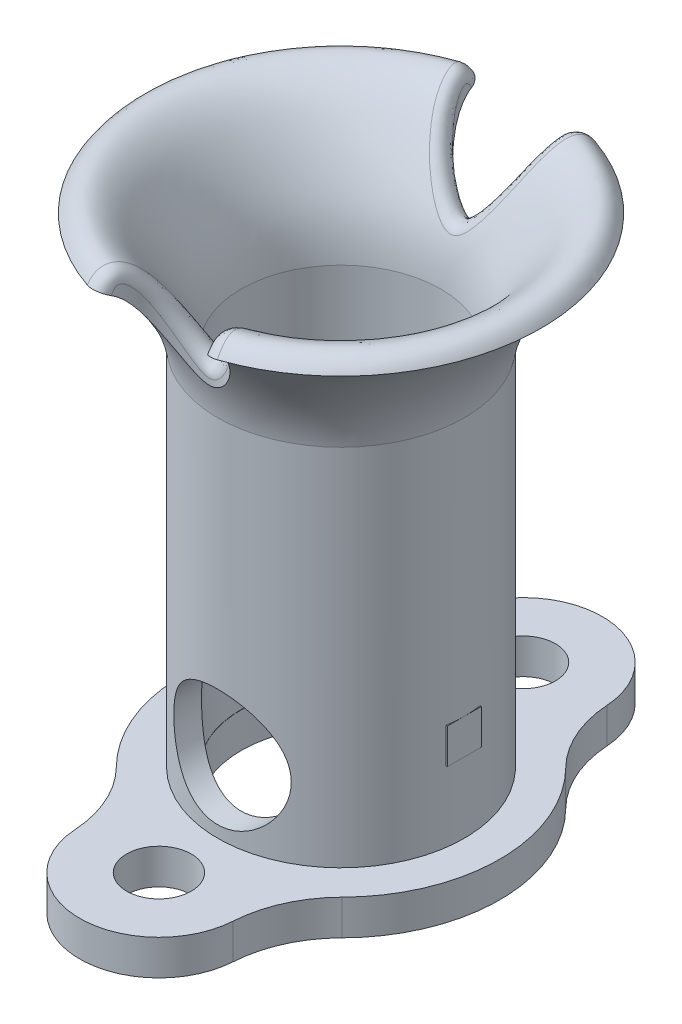
SolidWorks part; units mm, degrees
ref_plane "Front Plane" through (0, 0, 0) normal (0, 0, 1) x (1, 0, 0)
ref_plane "Top Plane" through (0, 0, 0) normal (0, 1, 0) x (1, 0, 0)
ref_plane "Right Plane" through (0, 0, 0) normal (1, 0, 0) x (0, 0, -1)
sketch "Sketch1" plane through (0, 0, 0) normal (0, 0, 1) x (1, 0, 0)
  line L0 (0, 0) -> (-8.5, 0) construction
  line L1 (-8.5, 0) -> (-8.5, 25)
  line L3 (-10.5, 0) -> (-10.5, 25)
  line L5 (0, 0) -> (0, 26.9305) construction
  line L6 (-10.5, 0) -> (-10.5, -6)
  line L7 (-10.5, -6) -> (-8.5, -6)
  line L8 (-8.5, -6) -> (-8.5, 0)
  spline S0 degree 3 poles (-8.5, 25) (-8.597, 26.015) (-8.907, 27.9673) (-10.2035, 30.7165) (-11.7469, 33.1056) (-13.7772, 35.5008) (-16.0448, 36.4741) (-17.0155, 34.8472) knots 0 0 0 0 0.199433 0.381103 0.589074 0.751073 1 1 1 1
  spline S1 degree 3 poles (-17.0155, 34.8472) (-15.0617, 34.1491) (-12.5469, 30.7995) (-10.7724, 27.1394) (-10.5, 25) knots 0 0 0 0 0.483303 1 1 1 1
  dimension "D1" = 8.5
  dimension "D2" = 25
  dimension "D3" = 25
  dimension "D4" = 6
revolve "Revolve1" add sketch "Sketch1" angle 360 about L5
sketch "Sketch3" plane through (0, 0, 0) normal (0, 0, 1) x (1, 0, 0)
  line L1 (-2.5, 0) -> (10.5, 0)
  line L2 (-2.5, 0) -> (-2.5, 3)
  line L3 (-2.5, 3) -> (10.5, 3)
  line L4 (10.5, 0) -> (10.5, 3)
  line L5 (10.5, -6) -> (10.5, 25) construction
  line L6 (-2.5, 1.5) -> (0, 1.5) construction
  line L7 (0, 1.5) -> (0, 0) construction
  line L8 (-2.5, 0) -> (-2.5, -6) construction
  line L9 (-10.5, -6) -> (10.5, -6) construction
  circle A0 centre (0, 1.5) radius 0.5
  dimension "D3" = 1
  dimension "D1" = 3
  dimension "D2" = 13
extrude "Boss-Extrude1" add sketch "Sketch3" along normal blind 1.45 and the other way blind 1.45
sketch "Sketch4" plane through (0, 0, 1.45) normal (0, 0, 1) x (1, 0, 0)
  circle A0 centre (0, 0) radius 5
  dimension "D1" = 10
extrude "Cut-Extrude1" cut sketch "Sketch4" along normal blind 20
sketch "Sketch7" plane through (0, -6, 0) normal (0, -1, 0) x (1, 0, 0)
  line L0 (0.024, 0.0249) -> (0.024, 15.5249) construction
  line L1 (0.024, 0.0249) -> (4.156, 0.0249) construction
  circle A0 centre (0.024, 15.5249) radius 2.75
  circle A1 centre (0.024, -15.4751) radius 2.75
  circle A2 centre (0.024, 0.0249) radius 8.5
  arc A3 (6.7605, -15.9004) -> (-6.7127, -15.8998) centre (0.024, -15.4751) cw
  arc A4 (6.7606, 15.9488) -> (-6.7128, 15.9482) centre (0.024, 15.5249) ccw
  arc A5 (-9.5867, 9.5397) -> (-6.7128, 15.9482) centre (-16.6931, 16.5752) ccw
  arc A6 (9.6354, -9.4938) -> (9.6356, 9.5401) centre (0.0257, 0.0232) ccw
  arc A7 (-9.5867, 9.5397) -> (-9.5865, -9.4935) centre (0.0257, 0.0232) ccw
  arc A8 (-6.7127, -15.8998) -> (-9.5865, -9.4935) centre (-16.6928, -16.5291) ccw
  arc A9 (9.6356, 9.5401) -> (6.7606, 15.9488) centre (16.7409, 16.5767) cw
  arc A10 (9.6354, -9.4938) -> (6.7605, -15.9004) centre (16.7407, -16.5306) ccw
extrude "Boss-Extrude3" add sketch "Sketch7" along normal blind 3
sketch "Sketch8" plane through (0, -6, 0) normal (0, 1, 0) x (1, 0, 0)
  line L0 (0, 0) -> (21.9292, 0) construction
  circle A2 centre (0.024, 15.4751) radius 4.25
  circle A3 centre (0.024, -15.4751) radius 4.25
  dimension "D1" = 8.5
extrude "Cut-Extrude4" cut sketch "Sketch8" along normal blind 53
fillet "Fillet4" radius 1 2 edges at (0.1467, 32.2609, 11.2268) (-0.1119, 32.2609, -11.2272)
